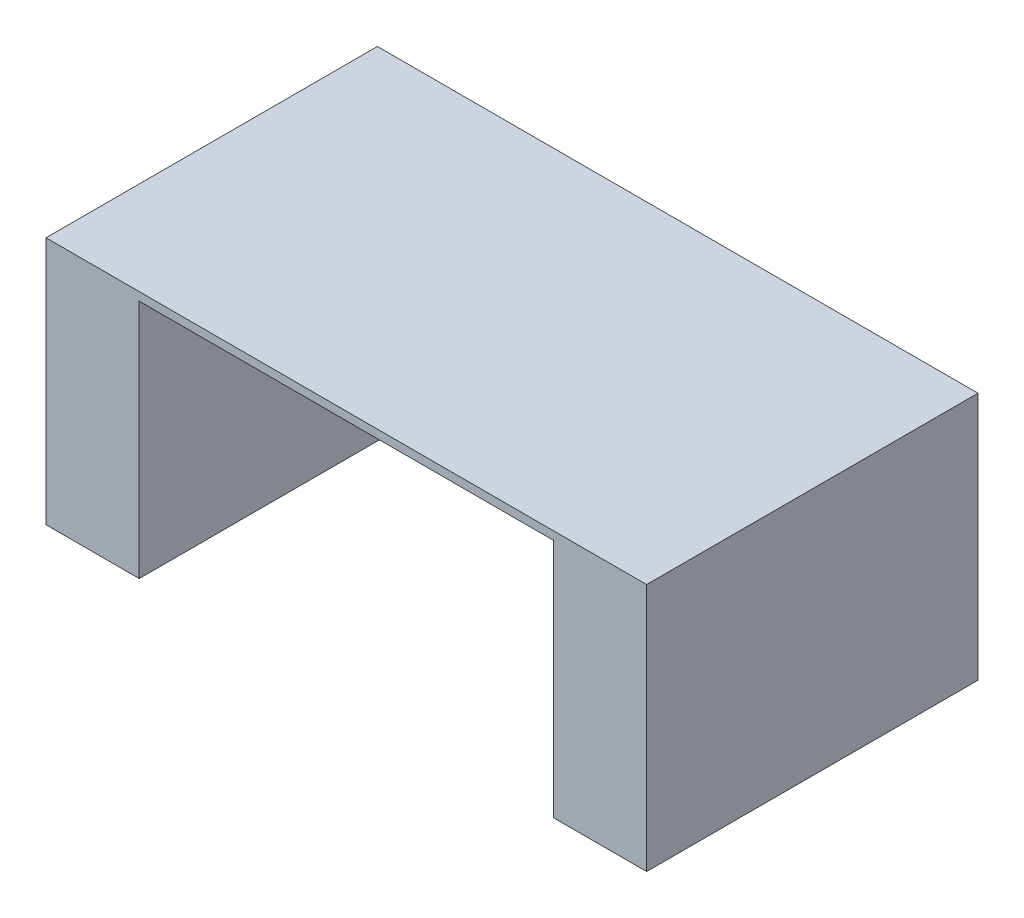
SolidWorks part; units mm, degrees
ref_plane "Front Plane" through (0, 0, 0) normal (0, 0, 1) x (1, 0, 0)
ref_plane "Top Plane" through (0, 0, 0) normal (0, 1, 0) x (1, 0, 0)
ref_plane "Right Plane" through (0, 0, 0) normal (1, 0, 0) x (0, 0, -1)
sketch "Sketch4" plane through (0, 0, 0) normal (0, 1, 0) x (1, 0, 0)
  line L1 (-145, 80) -> (145, 80)
  line L2 (-145, 80) -> (-145, -80)
  line L3 (-145, -80) -> (145, -80)
  line L4 (145, 80) -> (145, -80)
  line L5 (-145, 80) -> (145, -80) construction
  line L6 (-145, -80) -> (145, 80) construction
  point P0 (0, 0)
  dimension "D1" = 160
  dimension "D2" = 290
extrude "Boss-Extrude3" add sketch "Sketch4" along normal blind 120
sketch "Sketch5" plane through (0, 0, 0) normal (0, 1, 0) x (1, 0, 0)
  line L1 (-100, 80) -> (100, 80)
  line L2 (-100, 80) -> (-100, -80)
  line L3 (-100, -80) -> (100, -80)
  line L4 (100, 80) -> (100, -80)
  line L5 (-100, 80) -> (100, -80) construction
  line L6 (-100, -80) -> (100, 80) construction
  point P0 (0, 0)
  dimension "D1" = 160
  dimension "D2" = 200
extrude "Cut-Extrude2" cut sketch "Sketch5" along normal blind 116
